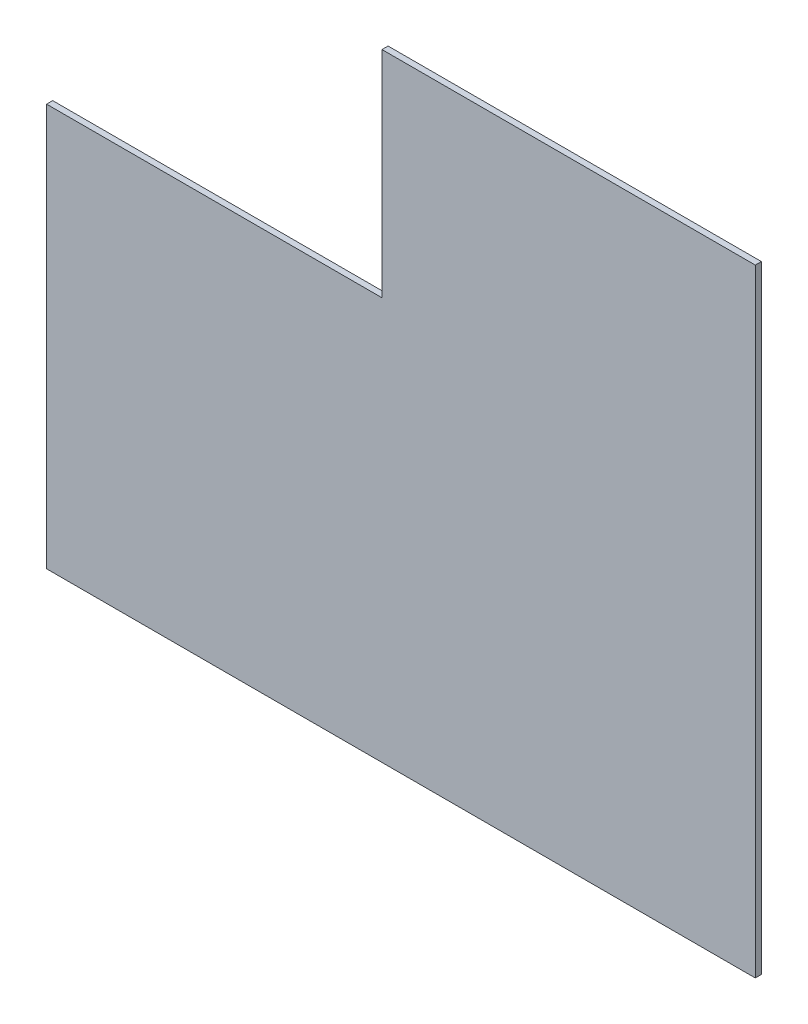
SolidWorks part; units mm, degrees
ref_plane "Спереди" through (0, 0, 0) normal (0, 0, 1) x (1, 0, 0)
ref_plane "Сверху" through (0, 0, 0) normal (0, 1, 0) x (1, 0, 0)
ref_plane "Справа" through (0, 0, 0) normal (1, 0, 0) x (0, 0, -1)
other "Configuration Table"
sketch "Эскиз2" plane through (0, 0, 0) normal (0, 0, 1) x (1, 0, 0)
  line L0 (527, 153.715) -> (0, 153.715) construction
  line L1 (1162.3, -506.285) -> (0, -506.285)
  line L2 (1162.3, -506.285) -> (1162.3, 506.285)
  line L3 (1162.3, 506.285) -> (550, 506.285)
  line L6 (0, -506.285) -> (0, 153.715)
  line L7 (0, 153.715) -> (550, 153.715)
  line L11 (550, 153.715) -> (550, 506.285)
  line L15 (550, 456.285) -> (550, 496.285) construction
  line L16 (1162.3, 506.285) -> (540, 506.285) construction
  point P13 (570.4121, 506.285)
extrude "Бобышка-Вытянуть1" add sketch "Эскиз2" against normal blind 10
equation "\"Ширина груза\"= 420"
equation "\"Глубина груза\"= 490"
equation "\"Высота груза\"= 297"
equation "\"Ширина ячейки\"= \"Ширина груза\" + 10"
equation "\"Глубина ячейки\"= \"Глубина груза\" + 10"
equation "\"Высота ячейки\"= \"Высота груза\" + 10 + 13"
equation "\"Колво ячеек ширина\"= 2"
equation "\"Колво ячеек высота\"= 2"
equation "\"Толщина стенки\"= 10"
equation "\"Крепление дверцы\"= 5"
equation "\"Ширина рейки\"= \"Толщина шестерни\""
equation "\"Высота рейки\"= 20"
equation "\"Высота пола\"= 20"
equation "\"Колво полозьев\"= 5"
equation "\"Отступ рейки\"= 20"
equation "\"Глубина каретки\"= \"Глубина ячейки\" + 30 + \"Мотор Y высота корпуса\" + 20"
equation "\"Длинна рейки\"= ( \"Ширина ячейки\" + \"Толщина стенки\" + \"Крепление дверцы\" ) * \"Колво ячеек ширина\" + \"Ширина ячейки выгрузки\" * \"Колво выгрузки\" + \"Толщина стенки\""
equation "\"Отступ шпильки\"= 26"
equation "\"Диаметр шпильки\"= 5"
equation "\"Длинна шпильки\"= ( \"Высота ячейки\" + \"Толщина стенки\" + \"Высота пола\" ) * \"Колво ячеек высота\" + ( \"Толщина стенки\" + \"Отступ рейки\" ) * 2 "
equation "\"Ширина пластины\"= 50  "
equation "\"Высота зона выгрузки\"= \"Высота ячейки\" * 2 + \"Толщина стенки\" * 2"
equation "\"Колво выгрузки\"= 1"
equation "\"Ширина ячейки выгрузки\"= \"Ширина ячейки\" + \"Толщина стенки\" + \"Отступ крепления мотора фиксации\"*2"
equation "\"Отступ крепления мотора фиксации\" = 30"
equation "\"Мотор X ширина корпуса\"= 42.3"
equation "\"Мотор X высота корпуса\"= 42.3"
equation "\"Мотор X длина корпуса\"= 40"
equation "\"Мотор X вылет вала\"= 19.8"
equation "\"Мотор Y ширина корпуса\"= 42.3"
equation "\"Мотор Y высота корпуса\"= 42.3"
equation "\"Мотор Y длина корпуса\"= 48"
equation "\"Мотор Y вылет вала\"= 30"
equation "\"Мотор Z ширина корпуса\"= 42"
equation "\"Мотор Z высота корпуса\"= 42"
equation "\"Мотор Z длина корпуса\"= 40"
equation "\"Мотор Z вылет вала\"= 23"
equation "\"Мотор диаметр вала ПРЕДВ\"= 5"
equation "\"Мотор шаг крепления ПРЕДВ\"= 31"
equation "\"Мотор диаметр отверстий ПРЕДВ\"= 3"
equation "\"Мотор глубина отверстий ПРЕДВ\"= 4.5"
equation "\"Мотор диаметр буртика ПРЕДВ\"= 22"
equation "\"Мотор высота буртика ПРЕДВ\"= 2"
equation "\"Мотор диаметр шкива ПРЕДВ\"= 16"
equation "\"Мотор длина шкива ПРЕДВ\"= 12"
equation "\"Мотор отступ шкива ПРЕДВ\"= 5"
equation "\"Мотор X шаг градусов\"= 1.8"
equation "\"Мотор Y шаг градусов\"= 1.8"
equation "\"Мотор Z шаг градусов\"= 1.8"
equation "\"Мотор Y диаметр ротора\"= 25.78"
equation "\"Толщина шестерни\"= 10"
equation "\"D1@Бобышка-Вытянуть1\"=\"Толщина стенки\""
